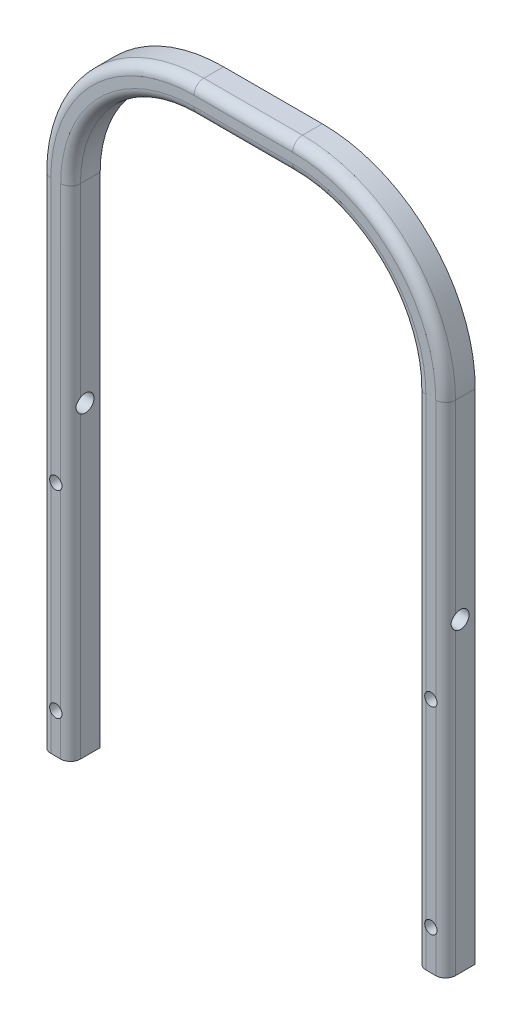
SolidWorks part; units mm, degrees
ref_plane "Plan de face" through (0, 0, 0) normal (0, 0, 1) x (1, 0, 0)
ref_plane "Plan de dessus" through (0, 0, 0) normal (0, 1, 0) x (1, 0, 0)
ref_plane "Plan de droite" through (0, 0, 0) normal (1, 0, 0) x (0, 0, -1)
sketch "Esquisse1" plane through (0, 0, 0) normal (0, 0, 1) x (1, 0, 0)
  line L0 (0, 0) -> (0, 126) construction
  line L1 (35, 0) -> (35, 126)
  line L2 (35, 126) -> (-35, 126)
  line L3 (35, 0) -> (41, 0)
  line L4 (41, 0) -> (41, 132)
  line L5 (41, 132) -> (-41, 132)
  line L6 (-41, 0) -> (-41, 132)
  line L7 (-35, 0) -> (-41, 0)
  line L8 (-35, 0) -> (-35, 126)
  point P12 (0, 132)
  dimension "D1" = 6
  dimension "D2" = 70
  dimension "D3" = 126
  dimension "D4" = 6
extrude "Boss.-Extru.1" add sketch "Esquisse1" along normal blind 6
sketch "Esquisse2" plane through (0, 0, 6) normal (0, 0, 1) x (1, 0, 0)
  line L0 (-38, 0) -> (-38, 48) construction
  line L1 (-41, 0) -> (-35, 0) construction
  line L2 (0, 0) -> (0, 126) construction
  line L3 (-35, 126) -> (35, 126) construction
  line L4 (38, 0) -> (38, 48) construction
  circle A0 centre (-38, 48) radius 1.25
  circle A1 centre (-38, 8) radius 1.25
  circle A2 centre (38, 8) radius 1.25
  circle A3 centre (38, 48) radius 1.25
  dimension "D1" = 2.5
  dimension "D2" = 40
  dimension "D3" = 8
extrude "Enlèv. mat.-Extru.1" cut sketch "Esquisse2" against normal through all both and the other way through all
fillet "Congé1" radius 25 2 edges at (35, 126, 3) (-35, 126, 3)
fillet "Congé2" radius 31 2 edges at (41, 132, 3) (-41, 132, 3)
fillet "Congé3" radius 2 10 edges at (41, 50.5, 6) (31.9203, 122.9203, 6) (0, 132, 6) (-41, 50.5, 6) (-35, 50.5, 6) (35, 50.5, 6) (27.6777, 118.6777, 6) (0, 126, 6) (-31.9203, 122.9203, 6) (-27.6777, 118.6777, 6)
sketch "Esquisse3" plane through (41, 0, 0) normal (1, 0, 0) x (0, 0, -1)
  line L0 (0, 62) -> (-3, 62) construction
  line L1 (0, 0) -> (0, 101) construction
  line L2 (-4, 0) -> (0, 0) construction
  circle A0 centre (-3, 62) radius 1.75
  dimension "D1" = 3.5
  dimension "D3" = 62
  dimension "D2" = 3
extrude "Enlèv. mat.-Extru.2" cut sketch "Esquisse3" against normal through all both and the other way through all
